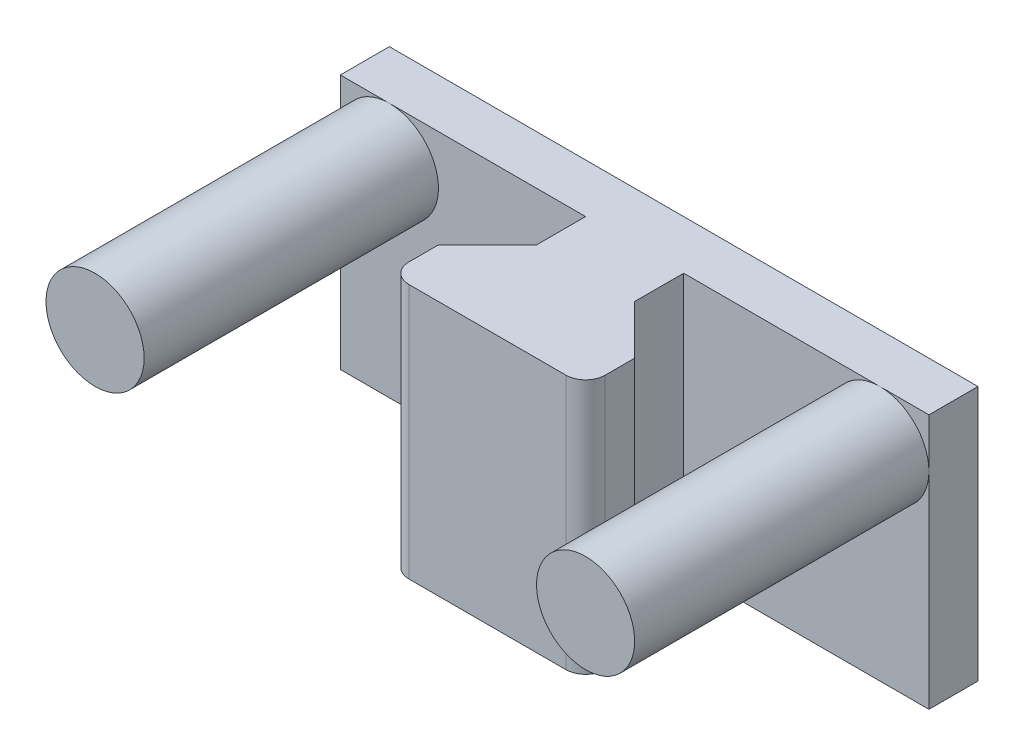
SolidWorks part; units mm, degrees
ref_plane "Front Plane" through (0, 0, 0) normal (0, 0, 1) x (1, 0, 0)
ref_plane "Top Plane" through (0, 0, 0) normal (0, 1, 0) x (1, 0, 0)
ref_plane "Right Plane" through (0, 0, 0) normal (1, 0, 0) x (0, 0, -1)
sketch "Sketch1" plane through (0, 0, 0) normal (0, 1, 0) x (1, 0, 0)
  line L0 (10, 0) -> (-10, 0)
  line L1 (-10, 0) -> (-10, 5)
  line L2 (-10, 5) -> (-5, 5)
  line L3 (-5, 5) -> (-5, 15)
  line L4 (-5, 15) -> (-30, 15)
  line L5 (-30, 15) -> (-30, 20)
  line L6 (-30, 20) -> (30, 20)
  line L7 (0, 20) -> (0, 0)
  line L8 (30, 15) -> (30, 20)
  line L9 (5, 15) -> (30, 15)
  line L10 (5, 5) -> (5, 15)
  line L11 (10, 5) -> (5, 5)
  line L12 (10, 0) -> (10, 5)
  dimension "D1" = 10
  dimension "D2" = 5
  dimension "D3" = 10
  dimension "D4" = 30
  dimension "D5" = 5
  dimension "D6" = 5
extrude "Boss-Extrude1" add sketch "Sketch1" along normal blind 26 contours L7 L6 L5 L4 L3 L2 L1 L0 | L0 L12 L11 L10 L9 L8 L6 L7 region at (5, 0, -0.3606) region at (-5, 0, -0.3606)
sketch "Sketch2" plane through (0, 0, -15) normal (0, 0, 1) x (1, 0, 0)
  line L1 (-5, 26) -> (-30, 26) construction
  line L2 (-30, 26) -> (-30, 0) construction
  circle A0 centre (-25, 21) radius 5
  dimension "D1" = 10
extrude "Boss-Extrude2" add sketch "Sketch2" along normal blind 30 contours A0
mirror "Mirror1" about plane through (0, 0, 0) normal (1, 0, 0) of "Boss-Extrude2"
fillet "Fillet1" radius 2 2 edges at (10, 13, 0) (-10, 13, 0)
chamfer "Chamfer1" distance 5 angle 45 2 edges at (5, 13, -5) (-5, 13, -5)
equation "\"shaftDiam\" = 20mm"
equation "\"keyW\" = 8mm"
equation "\"keyL\" = 10mm"
equation "\"clearance\" = .8mm"
equation "\"handleShaftLen\" = 60mm"
equation "\"panelH\" = 80mm"
equation "\"panelW\" = 110mm"
equation "\"D1@Sketch1\"=\"shaftDiam\"/2"
equation "\"D2@Sketch1\"=\"shaftDiam\"/4"
equation "\"D3@Sketch1\"=\"shaftDiam\"/2"
equation "\"D4@Sketch1\"= \"shaftDiam\" * 1.5"
equation "\"D5@Sketch1\"=\"shaftDiam\"/4"
equation "\"D6@Sketch1\"=\"shaftDiam\"/4"
equation "\"D1@Boss-Extrude1\"= \"shaftDiam\" + \"handleShaftLen\" / 10"
equation "\"D1@Sketch2\"=\"shaftDiam\"/2"
equation "\"D1@Boss-Extrude2\"=\"shaftDiam\"*1.5"
equation "\"D1@Fillet1\"=\"shaftDiam\"/10"
equation "\"D1@Chamfer1\"= \"shaftDiam\" / 4"
